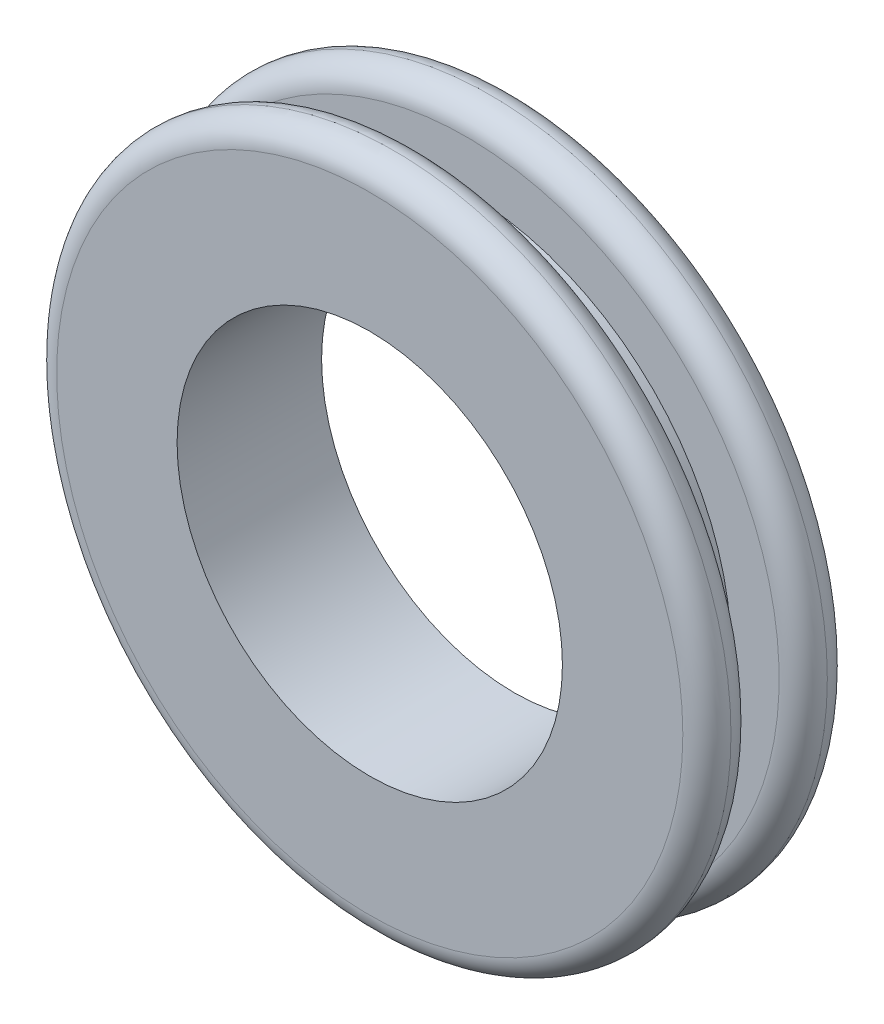
SolidWorks part; units mm, degrees
material "6061 合金"
ref_plane "前视基准面" through (0, 0, 0) normal (0, 0, 1) x (1, 0, 0)
ref_plane "上视基准面" through (0, 0, 0) normal (0, 1, 0) x (1, 0, 0)
ref_plane "右视基准面" through (0, 0, 0) normal (1, 0, 0) x (0, 0, -1)
sketch "草图1" plane through (0, 0, 0) normal (0, 0, 1) x (1, 0, 0)
  circle A0 centre (0, 0) radius 4
  circle A1 centre (0, 0) radius 7
  dimension "D1" = 8
  dimension "D2" = 14
extrude "凸台-拉伸1" add sketch "草图1" along normal blind 3
sketch "草图2" plane through (0, 0, 0) normal (1, 0, 0) x (0, 0, -1)
  line L0 (1.5109, 0) -> (-6.253, 0) construction
  line L2 (-3, 7) -> (-3, -7) construction
  line L3 (-2, 7) -> (-1, 7)
  line L4 (-2, 7) -> (-2, 5.5)
  line L5 (-2, 5.5) -> (-1, 5.5)
  line L6 (-1, 7) -> (-1, 5.5)
  dimension "D1" = 1
  dimension "D2" = 1
  dimension "D3" = 1.5
  dimension "D4" = 5.5
revolve "切除-旋转1" cut sketch "草图2" angle 360 about L0
fillet "圆角1" radius 0.5 4 edges at (-7, 0, 2) (-7, 0, 1) (7, 0, 0) (7, 0, 3)
